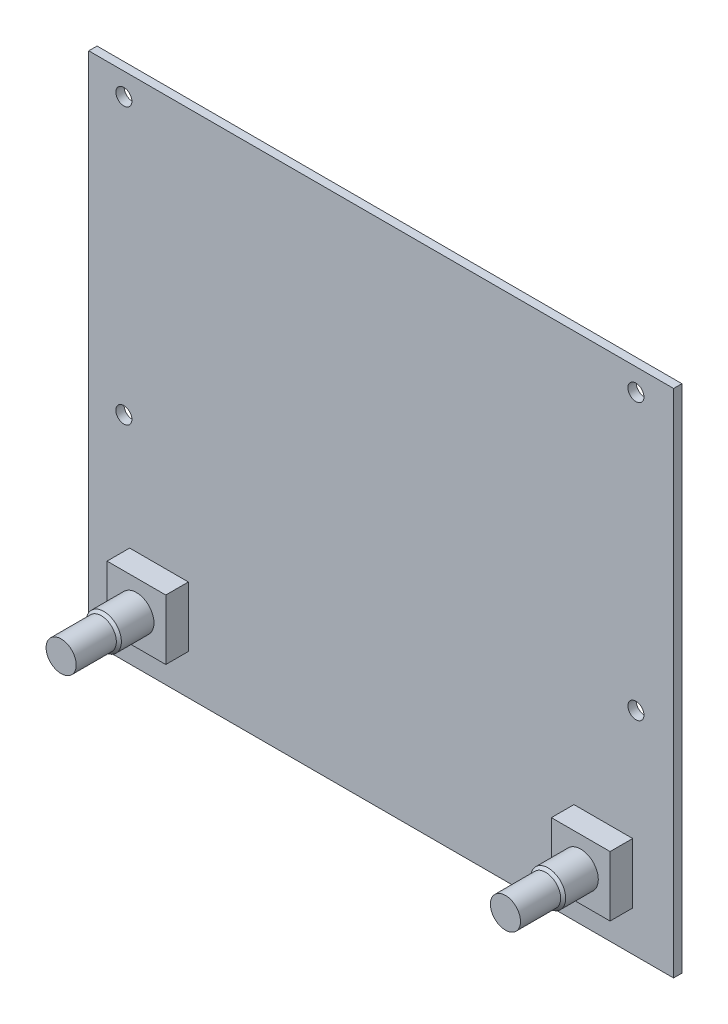
SolidWorks part; units mm, degrees
ref_plane "Front Plane" through (0, 0, 0) normal (0, 0, 1) x (1, 0, 0)
ref_plane "Top Plane" through (0, 0, 0) normal (0, 1, 0) x (1, 0, 0)
ref_plane "Right Plane" through (0, 0, 0) normal (1, 0, 0) x (0, 0, -1)
sketch "Sketch1" plane through (0, 0, 0) normal (0, 0, 1) x (1, 0, 0)
  line L1 (-58.2701, 50.8698) -> (58.2701, 50.8698)
  line L2 (-58.2701, 50.8698) -> (-58.2701, -50.8698)
  line L3 (-58.2701, -50.8698) -> (58.2701, -50.8698)
  line L4 (58.2701, 50.8698) -> (58.2701, -50.8698)
  line L5 (-58.2701, 50.8698) -> (58.2701, -50.8698) construction
  line L6 (-58.2701, -50.8698) -> (58.2701, 50.8698) construction
  circle A0 centre (-51.2699, 46.4502) radius 1.6002
  circle A1 centre (50.7695, 46.4502) radius 1.6002
  circle A2 centre (50.7695, -8.4493) radius 1.6002
  circle A3 centre (-51.2699, -8.4493) radius 1.6002
  point P0 (0, 0)
  dimension "D3" = 3.2004
  dimension "D6" = 3.2004
  dimension "D7" = 3.2004
  dimension "D8" = 3.2004
  dimension "D1" = 101.7397
  dimension "D2" = 116.5403
  dimension "D4" = 7.0002
  dimension "D5" = 4.4196
  dimension "D9" = 7.5006
  dimension "D10" = 54.8996
extrude "Boss-Extrude1" add sketch "Sketch1" along normal blind 1.6561
sketch "Sketch2" plane through (0, 0, 1.6561) normal (0, 0, 1) x (1, 0, 0)
  line L0 (0, 50.8698) -> (0, -50.8698) construction
  line L1 (-50.1193, -42.8688) -> (-38.42, -42.8688)
  line L2 (-50.1193, -42.8688) -> (-50.1193, -30.8699)
  line L3 (-50.1193, -30.8699) -> (-38.42, -30.8699)
  line L4 (-38.42, -42.8688) -> (-38.42, -30.8699)
  line L5 (58.2701, 50.8698) -> (-58.2701, 50.8698) construction
  line L36 (-58.2701, -50.8698) -> (58.2701, -50.8698) construction
  line L37 (50.1193, -30.8699) -> (38.42, -30.8699)
  line L38 (38.42, -42.8688) -> (38.42, -30.8699)
  line L39 (50.1193, -42.8688) -> (38.42, -42.8688)
  line L40 (50.1193, -42.8688) -> (50.1193, -30.8699)
  dimension "D1" = 8.1509
  dimension "D2" = 8.001
  dimension "D3" = 11.6992
  dimension "D4" = 11.999
  dimension "D5" = 8.1509
  dimension "D6" = 8.001
  dimension "D7" = 11.6992
  dimension "D8" = 11.999
extrude "Boss-Extrude2" add sketch "Sketch2" along normal blind 4.5
sketch "Sketch3" plane through (0, 0, 6.1561) normal (0, 0, 1) x (1, 0, 0)
  line L0 (-44.2697, -42.8688) -> (-44.2697, -30.8699) construction
  line L1 (-50.1193, -42.8688) -> (-38.42, -42.8688) construction
  line L2 (-38.42, -30.8699) -> (-50.1193, -30.8699) construction
  line L3 (-50.1193, -36.8694) -> (-38.42, -36.8694) construction
  line L4 (-50.1193, -30.8699) -> (-50.1193, -42.8688) construction
  line L5 (-38.42, -42.8688) -> (-38.42, -30.8699) construction
  line L6 (38.42, -42.8688) -> (50.1193, -30.8699) construction
  line L7 (50.1193, -42.8688) -> (38.42, -30.8699) construction
  circle A0 centre (-44.2697, -36.8694) radius 3.5
  circle A1 centre (44.2697, -36.8694) radius 3.5
  point P16 (-44.2697, -36.8694)
  point P26 (44.2697, -36.8694)
  dimension "D1" = 7
  dimension "D2" = 7
extrude "Boss-Extrude3" add sketch "Sketch3" along normal blind 7
chamfer "Chamfer1" distance 0.5 angle 45 2 edges at (-40.7697, -36.8694, 13.1561) (47.7697, -36.8694, 13.1561)
sketch "Sketch5" plane through (0, 0, 13.1561) normal (0, 0, 1) x (1, 0, 0)
  circle A0 centre (44.2697, -36.8694) radius 3 construction
  circle A1 centre (-44.2697, -36.8694) radius 3 construction
  circle A2 centre (44.2697, -36.8694) radius 3
  circle A3 centre (-44.2697, -36.8694) radius 3
extrude "Boss-Extrude4" add sketch "Sketch5" along normal blind 8
sketch "Sketch6" plane through (0, 0, 0) normal (0, 0, -1) x (-1, 0, 0)
  line L0 (-58.2701, 50.8698) -> (58.2701, 50.8698) construction
  line L1 (-37.7952, 36.4553) -> (39.2557, 36.4553)
  line L2 (-37.7952, 36.4553) -> (-37.7952, 15.8052)
  line L3 (-37.7952, 15.8052) -> (39.2557, 15.8052)
  line L4 (39.2557, 36.4553) -> (39.2557, 15.8052)
  dimension "D1" = 14.4145
  dimension "D2" = 19.0144
  dimension "D3" = 77.0509
  dimension "D4" = 20.6502
extrude "Cut-Extrude1" cut sketch "Sketch6" against normal blind 1
